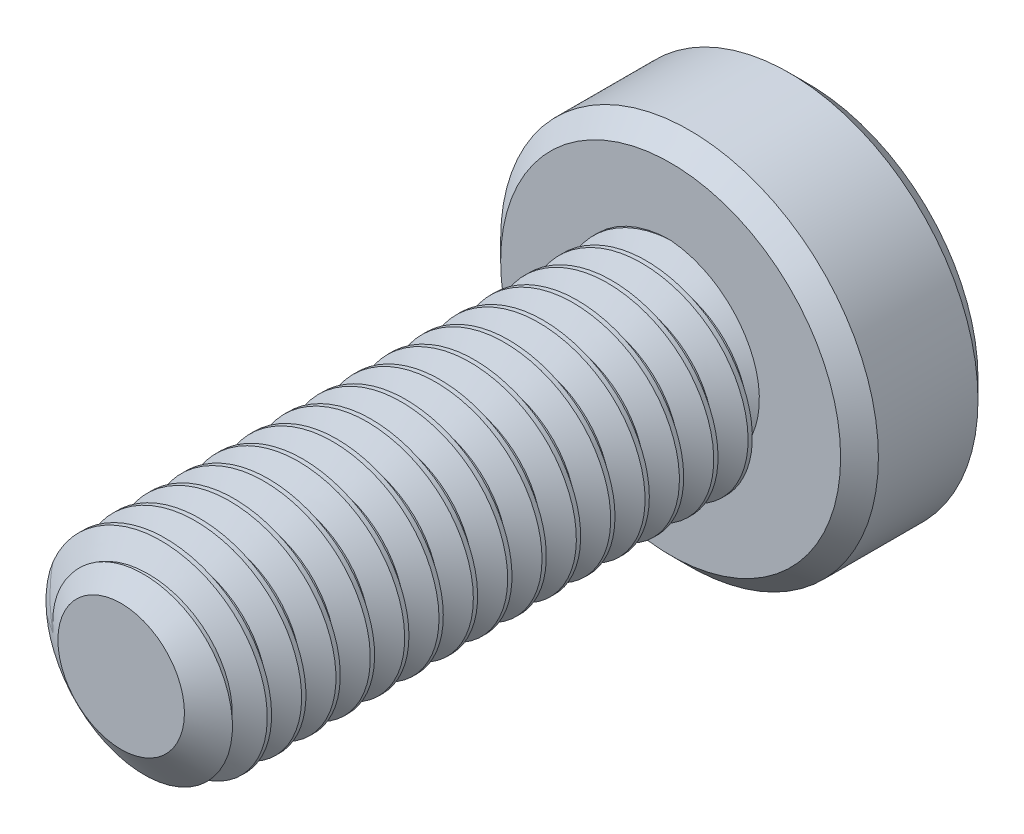
SolidWorks part; units mm, degrees
other "DetailItem1"
ref_plane "Front Plane" through (0, 0, 0) normal (0, 0, 1) x (1, 0, 0)
ref_plane "Top Plane" through (0, 0, 0) normal (0, 1, 0) x (1, 0, 0)
ref_plane "Right Plane" through (0, 0, 0) normal (1, 0, 0) x (0, 0, -1)
sketch "Sketch1" plane through (0, 0, 0) normal (0, 0, 1) x (1, 0, 0)
  circle A0 centre (0, 0) radius 1.5
  dimension "OD" = 3
extrude "Extrude1" add sketch "Sketch1" against normal blind 8
sketch "Sketch2" plane through (0, 0, 0) normal (0, 0, 1) x (1, 0, 0)
  circle A0 centre (0, 0) radius 1.5 construction
  circle A1 centre (0, 0) radius 1.5
curve "Helix/Spiral1" pitch 0.5 height 8.5 radius 1.5 centre (0, 0, 0) axis (0, 0, -1) start towards (0, 1, 0) parameters "pitch"=0.5
sketch "Sketch3" plane through (0, 0, 0) normal (1, 0, 0) x (0, 0, -1)
  line L0 (-0.4375, 1.5) -> (-0.25, 1.1752)
  line L1 (-0.25, 1.1752) -> (-0.1875, 1.1752)
  line L2 (-0.1875, 1.1752) -> (0, 1.5)
  line L3 (-0.4375, 1.5) -> (0, 1.5)
  line L4 (-0.2187, 1.5) -> (-0.2187, 1.1752) construction
  line L5 (-0.3438, 1.3376) -> (-0.0938, 1.3376) construction
  line L6 (0, 1.5) -> (0, -1.5) construction
  dimension "D1" = 0.0625
  dimension "D2" = 0.25
  dimension "D3" = 60
sweep "Cut-Sweep1" cut profiles "Sketch3" path "Helix/Spiral1" align with end faces yes
sketch "Sketch4" plane through (0, 0, 0) normal (1, 0, 0) x (0, 0, -1)
  line L0 (0.4053, 1.5) -> (0, 0.9212)
  line L1 (0, 0.9212) -> (0, 1.5)
  line L2 (0.4053, 1.5) -> (0, 1.5)
  line L3 (-0.4375, 1.5) -> (0, 1.5) construction
  line L4 (0, 0) -> (7.0209, 0) construction
  dimension "D1" = 55
  dimension "D2" = 0.254
revolve "Cut-Revolve1" cut sketch "Sketch4" angle 360 about L4
sketch "Sketch6" plane through (0, 0, -8) normal (0, 0, -1) x (-1, 0, 0)
  circle A0 centre (0, 0) radius 2.75
  dimension "head dia" = 5.5
extrude "Extrude2" add sketch "Sketch6" along normal blind 2
sketch "Sketch7" plane through (0, 0, -10) normal (0, 0, -1) x (-1, 0, 0)
  line L1 (0, 1.1547) -> (-1, 0.5774)
  line L2 (-1, 0.5774) -> (-1, -0.5774)
  line L3 (-1, -0.5774) -> (0, -1.1547)
  line L4 (0, -1.1547) -> (1, -0.5774)
  line L5 (1, -0.5774) -> (1, 0.5774)
  line L6 (1, 0.5774) -> (0, 1.1547)
  circle A0 centre (0, 0) radius 1 construction
  dimension "hex dia" = 2
extrude "Cut-Extrude1" cut sketch "Sketch7" against normal blind 1.5
sketch "Sketch8" plane through (0, 0, -10) normal (0, 0, -1) x (-1, 0, 0)
  circle A0 centre (0, 0) radius 1.1547
extrude "Cut-Extrude2" cut sketch "Sketch8" against normal through all draft 45
chamfer "Chamfer1" distance 0.275 angle 45 2 edges at (-2.75, 0, -10) (-2.75, 0, -8)
sketch "Sketch10" plane through (0, 0, -8) normal (0, 0, 1) x (1, 0, 0)
  circle A1 centre (0, 0) radius 1.5
  circle A2 centre (0, 0) radius 1.5
  dimension "D1" = 0
ref_plane "Plane1" through (0, 0, -38.1) normal (0, 0, 1) x (1, 0, 0)
extrude "partial thread" [suppressed] add sketch "Sketch10" along normal up to surface (8 mm away) separate body up to plane "Plane1"
chamfer "Chamfer2" [suppressed] distance 0.06 angle 45
combine bodies "Combine1" [suppressed] operation type add bodies to combine 107 108
sketch "Sketch9" plane through (0, 0, 0) normal (1, 0, 0) x (0, 0, -1)
  line L0 (0, 1.5) -> (0, -1.5) construction
  line L1 (1.25, 1.5) -> (1.25, -1.5) construction
  dimension "D1" = 1.25
equation "\"D3@Helix/Spiral1\" = \"screw length@Extrude1\"+\"pitch@Helix/Spiral1\""
equation "\"D1@Sketch3\" = \"pitch@Helix/Spiral1\"*.125"
equation "\"D2@Sketch3\" = \"pitch@Helix/Spiral1\"*.5"
equation "\"D1@Cut-Extrude1\" = \"hex dia@Sketch7\"*.75"
equation "\"D1@Chamfer1\" = \"head dia@Sketch6\"*.05"
equation "\"D1@Sketch9\" = \"pitch@Helix/Spiral1\"*2.5"
equation "\"D1@Chamfer2\"=\"OD@Sketch1\"*.02"
